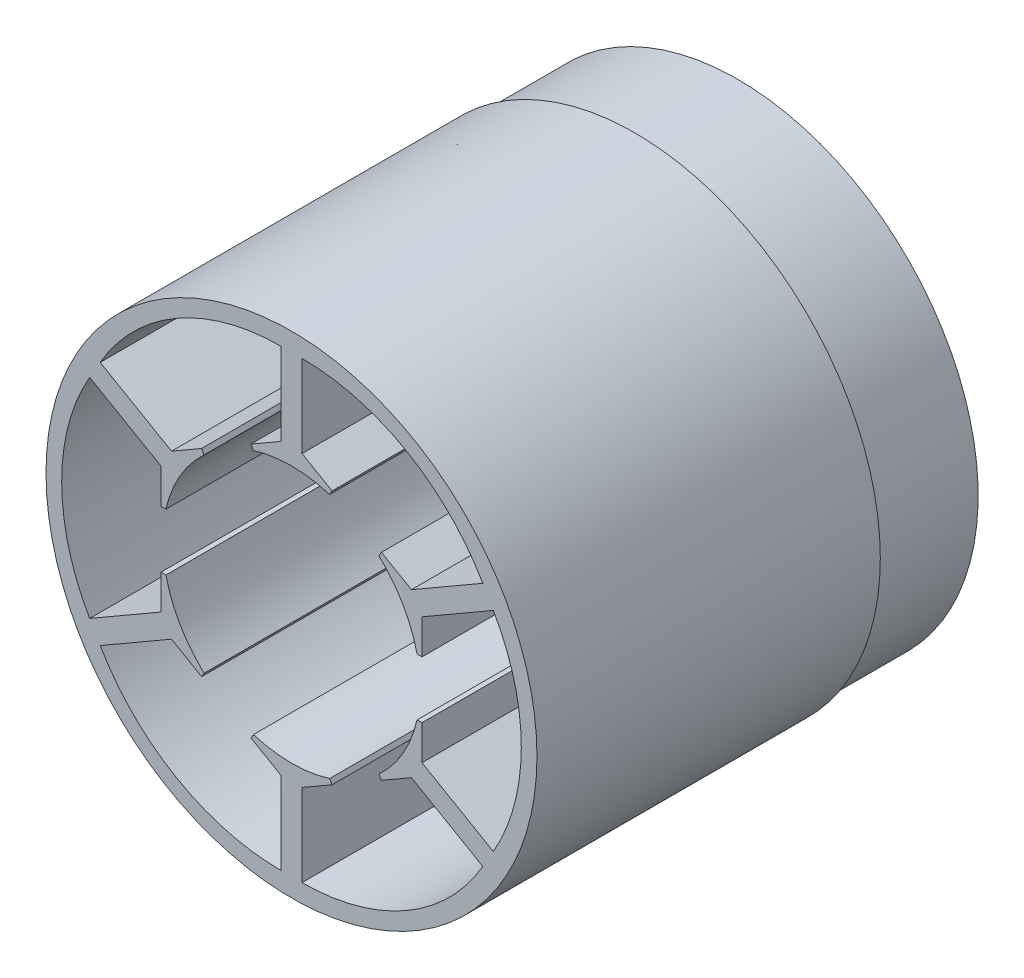
SolidWorks part; units mm, degrees
ref_plane "Front Plane" through (0, 0, 0) normal (0, 0, 1) x (1, 0, 0)
ref_plane "Top Plane" through (0, 0, 0) normal (0, 1, 0) x (1, 0, 0)
ref_plane "Right Plane" through (0, 0, 0) normal (1, 0, 0) x (0, 0, -1)
sketch "Motor_Base" plane through (0, 0, 0) normal (0, 0, 1) x (1, 0, 0)
  line L0 (0, 0) -> (0, 37.1463) construction
  line L1 (1.5331, 21.0694) -> (1.5331, 33.0694)
  line L2 (-1.5331, 21.0694) -> (-1.5331, 33.0694)
  line L3 (17.468, 11.8694) -> (27.8603, 17.8694)
  line L4 (19.0011, 9.214) -> (29.3934, 15.214)
  line L5 (19.0011, -9.186) -> (29.3934, -15.186)
  line L6 (17.468, -11.8414) -> (27.8603, -17.8414)
  line L7 (1.5331, -21.0414) -> (1.5331, -33.0414)
  line L8 (-1.5331, -21.0414) -> (-1.5331, -33.0414)
  line L9 (-17.468, -11.8414) -> (-27.8603, -17.8414)
  line L10 (-19.0011, -9.186) -> (-29.3934, -15.186)
  line L11 (-19.0011, 9.214) -> (-29.3934, 15.214)
  line L12 (-17.468, 11.8694) -> (-27.8603, 17.8694)
  line L13 (1.5331, 21.0694) -> (17.468, 11.8694)
  line L14 (-17.468, 11.8694) -> (-1.5331, 21.0694)
  line L15 (-19.0011, 9.214) -> (-19.0011, -9.186)
  line L16 (-17.468, -11.8414) -> (-1.5331, -21.0414)
  line L17 (1.5331, -21.0414) -> (17.468, -11.8414)
  line L18 (19.0011, -9.186) -> (19.0011, 9.214)
  line L20 (-9.5005, 16.4694) -> (-20.4004, 35.3485) construction
  line L23 (5.5682, 18.7398) -> (9.5005, 16.4694)
  line L25 (-15.9932, 24.7209) -> (-18.2032, 28.0912)
  line L27 (-13.4002, 26.2179) -> (-15.2139, 29.8171)
  line L28 (-15.9932, 24.7209) -> (-13.4002, 26.2179)
  line L29 (13.4123, 26.2109) -> (16.0053, 24.7139)
  line L30 (13.4123, 26.2109) -> (15.2261, 29.8101)
  line L31 (16.0053, 24.7139) -> (18.2154, 28.0842)
  line L32 (29.4055, 1.4901) -> (29.4055, -1.5041)
  line L33 (29.4055, 1.4901) -> (33.4293, 1.7189)
  line L34 (29.4055, -1.5041) -> (33.4293, -1.7329)
  line L35 (15.9932, -24.7209) -> (13.4002, -26.2179)
  line L36 (15.9932, -24.7209) -> (18.2032, -28.0912)
  line L37 (13.4002, -26.2179) -> (15.2139, -29.8171)
  line L38 (-13.4123, -26.2109) -> (-16.0053, -24.7139)
  line L39 (-13.4123, -26.2109) -> (-15.2261, -29.8101)
  line L40 (-16.0053, -24.7139) -> (-18.2154, -28.0842)
  line L41 (-29.4055, -1.4901) -> (-29.4055, 1.5041)
  line L42 (-29.4055, -1.4901) -> (-33.4293, -1.7189)
  line L43 (-29.4055, 1.5041) -> (-33.4293, 1.7329)
  line L44 (-15.9932, 24.7209) -> (-13.4002, 26.2179)
  line L45 (-13.0945, 14.3944) -> (-12.7312, 13.7651)
  line L46 (-5.9065, 18.5444) -> (-5.5432, 17.9151)
  line L47 (5.9187, 18.5374) -> (5.5553, 17.9081)
  line L49 (13.1067, 14.3874) -> (12.7434, 13.7581)
  line L50 (19.0011, 4.143) -> (18.2866, 4.143)
  line L52 (19.0011, -4.157) -> (18.2866, -4.157)
  line L53 (13.0824, -14.3734) -> (12.7312, -13.7651)
  line L55 (5.8944, -18.5234) -> (5.5432, -17.9151)
  line L56 (-5.9065, -18.5164) -> (-5.5553, -17.9081)
  line L58 (-13.0945, -14.3664) -> (-12.7434, -13.7581)
  line L59 (-19.0011, -4.143) -> (-18.2866, -4.143)
  line L61 (-19.0011, 4.157) -> (-18.2866, 4.157)
  circle A0 centre (0, 0) radius 35.75
  circle A4 centre (0, 0) radius 3.175
  circle A5 centre (0, 0) radius 18.75
  arc A6 (1.5331, 33.0694) -> (27.8603, 17.8694) centre (1.5331, 2.6694) cw
  circle A7 centre (0, 0) radius 4.7625
  arc A9 (29.3934, 15.214) -> (29.3934, -15.186) centre (3.0662, 0.014) cw
  arc A10 (27.8603, -17.8414) -> (1.5331, -33.0414) centre (1.5331, -2.6414) cw
  arc A11 (-1.5331, -33.0414) -> (-27.8603, -17.8414) centre (-1.5331, -2.6414) cw
  arc A12 (-29.3934, 15.214) -> (-29.3934, -15.186) centre (-3.0662, 0.014) ccw
  arc A13 (-27.8603, 17.8694) -> (-1.5331, 33.0694) centre (-1.5331, 2.6694) cw
  point P17 (0, 0)
  point P35 (0, 0.014)
  point P42 (9.5005, 16.4694)
  point P73 (0, 0)
  point P74 (-10.8113, 18.7398)
  point P99 (0, 0)
  dimension "D1" = 71.5
  dimension "D3" = 9.525
  dimension "D2" = 6.35
  dimension "D5" = 6
  dimension "D6" = 18.4
  dimension "D7" = 6
  dimension "D4" = 37.5
extrude "Stator_Shell" add sketch "Motor_Base" along normal blind 65 contours A0 | L18 L4 A9 L5 | A6 L3 L13 L1 | A10 L7 L17 L6 | A11 L9 L16 L8 | A12 L10 L15 L11 | A13 L2 L14 L12
extrude "Cut-Extrude1" cut sketch "Motor_Base<4>" along normal through all contours A5 A7 | A4 | A7 A4 region at (13.3758, 12.3711, 0) region at (0, 0, 0) region at (-4.6278, 0, 0)
sketch "Motor_Base<4>" plane through (0, 0, 0) normal (0, 0, 1) x (1, 0, 0) same geometry as "Motor_Base"
sketch "Stator_Lam_Support" plane through (0, 0, 0) normal (0, 0, -1) x (-1, 0, 0)
  line L0 (9.5005, 16.4694) -> (24.2852, 42.0991) construction
  line L1 (17.468, 11.8694) -> (1.5331, 21.0694) construction
  line L2 (14.3513, 31.3063) -> (13.5066, 28.0964)
  line L3 (13.5066, 28.0964) -> (17.56, 25.7582)
  line L4 (19.9157, 28.0964) -> (17.56, 25.7582)
  line L5 (34.2877, 3.2246) -> (31.0855, 2.3512)
  line L6 (34.2901, -3.1993) -> (31.0872, -2.3283)
  line L7 (31.0855, 2.3512) -> (31.0872, -2.3283)
  line L8 (19.9364, -28.0818) -> (17.579, -25.7452)
  line L9 (14.3744, -31.2957) -> (13.5273, -28.0865)
  line L10 (17.579, -25.7452) -> (13.5273, -28.0865)
  line L11 (-14.3513, -31.3063) -> (-13.5066, -28.0964)
  line L12 (-19.9157, -28.0964) -> (-17.56, -25.7582)
  line L13 (-13.5066, -28.0964) -> (-17.56, -25.7582)
  line L14 (-34.2877, -3.2246) -> (-31.0855, -2.3512)
  line L15 (-34.2901, 3.1993) -> (-31.0872, 2.3283)
  line L16 (-31.0855, -2.3512) -> (-31.0872, 2.3283)
  line L17 (-19.9364, 28.0818) -> (-17.579, 25.7452)
  line L18 (-14.3744, 31.2957) -> (-13.5273, 28.0865)
  line L19 (-17.579, 25.7452) -> (-13.5273, 28.0865)
  arc A0 (14.3513, 31.3063) -> (19.9157, 28.0964) centre (0, 0) cw
  arc A2 (34.2877, 3.2246) -> (34.2901, -3.1993) centre (0, 0) cw
  arc A3 (19.9364, -28.0818) -> (14.3744, -31.2957) centre (0, 0) cw
  arc A4 (-14.3513, -31.3063) -> (-19.9157, -28.0964) centre (0, 0) cw
  arc A5 (-34.2877, -3.2246) -> (-34.2901, 3.1993) centre (0, 0) cw
  arc A6 (-19.9364, 28.0818) -> (-14.3744, 31.2957) centre (0, 0) cw
  point P8 (1.5331, 33.0694)
  point P11 (15.5333, 26.9273)
  point P35 (0, 0)
  point P36 (0, 0)
extrude "Stator Lamination Support" add sketch "Stator_Lam_Support" against normal blind 16.35
sketch "Sketch6" plane through (0, 0, 65) normal (0, 0, 1) x (1, 0, 0)
  line L0 (9.5005, 16.4694) -> (18.75, 32.5036) construction
  line L1 (1.5331, 21.0694) -> (17.468, 11.8694) construction
  line L2 (14.4053, 16.6666) -> (11.564, 11.7412)
  line L3 (7.2157, 20.8139) -> (14.4053, 16.6666)
  line L4 (11.564, 11.7412) -> (4.3745, 15.8885)
  line L5 (4.3745, 15.8885) -> (7.2157, 20.8139)
  line L6 (21.6333, 4.158) -> (21.6363, -4.142)
  line L7 (15.9471, 4.1559) -> (21.6333, 4.158)
  line L8 (21.6363, -4.142) -> (15.9502, -4.1441)
  line L9 (15.9502, -4.1441) -> (15.9471, 4.1559)
  line L10 (14.4175, -16.656) -> (7.2311, -20.8086)
  line L11 (11.5727, -11.7327) -> (14.4175, -16.656)
  line L12 (7.2311, -20.8086) -> (4.3862, -15.8853)
  line L13 (4.3862, -15.8853) -> (11.5727, -11.7327)
  line L14 (-7.2157, -20.8139) -> (-14.4053, -16.6666)
  line L15 (-4.3745, -15.8885) -> (-7.2157, -20.8139)
  line L16 (-14.4053, -16.6666) -> (-11.564, -11.7412)
  line L17 (-11.564, -11.7412) -> (-4.3745, -15.8885)
  line L18 (-21.6333, -4.158) -> (-21.6363, 4.142)
  line L19 (-15.9471, -4.1559) -> (-21.6333, -4.158)
  line L20 (-21.6363, 4.142) -> (-15.9502, 4.1441)
  line L21 (-15.9502, 4.1441) -> (-15.9471, -4.1559)
  line L22 (-14.4175, 16.656) -> (-7.2311, 20.8086)
  line L23 (-11.5727, 11.7327) -> (-14.4175, 16.656)
  line L24 (-7.2311, 20.8086) -> (-4.3862, 15.8853)
  line L25 (-4.3862, 15.8853) -> (-11.5727, 11.7327)
  point P7 (10.8105, 18.7403)
  point P32 (0, 0)
  dimension "D1" = 4.15
extrude "Cut-Extrude3" cut sketch "Sketch6" against normal through all
sketch "Sketch7" plane through (0, 0, 0) normal (0, 0, -1) x (-1, 0, 0)
  circle A0 centre (0, 0) radius 35
  circle A1 centre (0, 0) radius 37.5
  dimension "D1" = 70
  dimension "D2" = 2.5
extrude "Base_Connection_Cut" cut sketch "Sketch7" against normal blind 15
